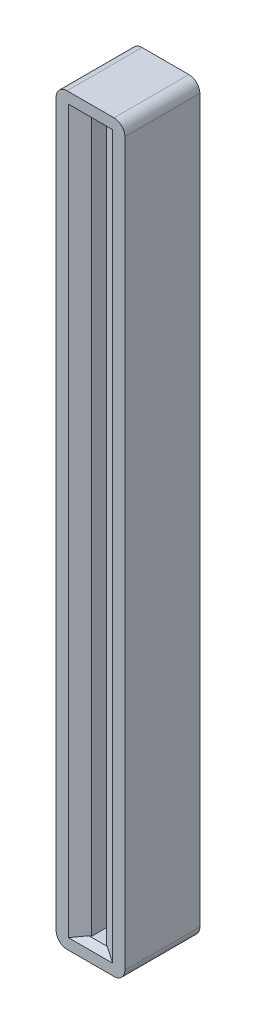
SolidWorks part; units mm, degrees
ref_plane "Front" through (0, 0, 0) normal (0, 0, 1) x (1, 0, 0)
ref_plane "Top" through (0, 0, 0) normal (0, 1, 0) x (1, 0, 0)
ref_plane "Right" through (0, 0, 0) normal (1, 0, 0) x (0, 0, -1)
sketch "Sketch1" plane through (0, 0, 0) normal (0, 0, 1) x (1, 0, 0)
  line L0 (0, -58.1025) -> (0, 58.1025) construction
  line L1 (-44.603, 0) -> (44.603, 0) construction
  line L2 (-5.0165, 61.9125) -> (5.0165, 61.9125)
  line L3 (5.0165, 61.9125) -> (5.0165, -61.9125)
  line L4 (-5.0165, 61.9125) -> (-5.0165, -61.9125)
  line L5 (-5.0165, -61.9125) -> (5.0165, -61.9125)
  point P0 (0, -61.9125)
  point P9 (0, 61.9125)
  point P11 (-5.0165, 0)
  point P12 (5.0165, 0)
  point P13 (0, 0)
  dimension "D1" = 123.825
  dimension "D2" = 10.033
  dimension "D3" = 116.205
sketch "Sketch2" plane through (0, 0, 0) normal (0, 0, 1) x (1, 0, 0)
  line L2 (-5.0165, 54.2925) -> (5.0165, 54.2925)
  line L3 (5.0165, 54.2925) -> (5.0165, -54.2925)
  line L4 (0, 54.2925) -> (0, 0) construction
  line L5 (0, 0) -> (5.0165, 0) construction
  line L6 (-5.0165, 54.2925) -> (-5.0165, -54.2925)
  line L7 (-5.0165, -54.2925) -> (5.0165, -54.2925)
  point P9 (-5.0165, 0)
  dimension "D1" = 10.033
  dimension "D2" = 108.585
extrude "Extrude2" add sketch "Sketch2" along normal blind 10.9474
fillet "Fillet1" radius 1.5875 4 edges at (5.0165, 54.2925, 5.4737) (5.0165, -54.2925, 5.4737) (-5.0165, -54.2925, 5.4737) (-5.0165, 54.2925, 5.4737)
sketch "Sketch7" plane through (0, 0, 10.9474) normal (0, 0, 1) x (1, 0, 0)
  line L0 (1.0795, -52.07) -> (1.0795, 52.07)
  line L1 (1.0795, 52.07) -> (-1.0795, 52.07)
  line L2 (0, 0) -> (2.159, 0) construction
  line L9 (-1.0795, -52.07) -> (-1.0795, 52.07)
  line L10 (1.0795, -52.07) -> (-1.0795, -52.07)
  line L11 (0, 0) -> (0, 53.4946) construction
  point P0 (1.0795, 0)
  point P5 (0, 52.07)
  point P8 (-1.0795, 0)
  dimension "D1" = 104.14
  dimension "D2" = 2.159
extrude "Cut-Extrude2" cut sketch "Sketch7" against normal blind 6.731
chamfer "Chamfer1" distance 2.159 angle 30 2 edges at (1.0795, 0, 10.9474) (-1.0795, 0, 10.9474) first distance on face at (0, 0, 10.9474)
chamfer "Chamfer2" distance 0.635 angle 60 2 edges at (0, 52.07, 10.9474) (0, -52.07, 10.9474) first distance on face at (0, 0, 10.9474)
